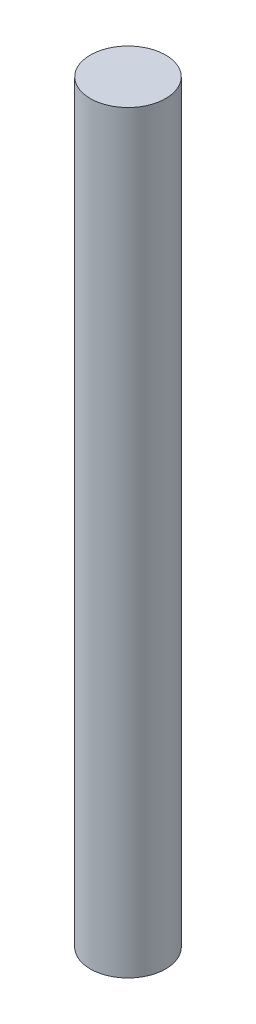
SolidWorks part; units mm, degrees
other "Title Block Table1"
other "DetailItem1"
material "PA Type 6 - Black"
ref_plane "Front Plane" through (0, 0, 0) normal (0, 0, 1) x (1, 0, 0)
ref_plane "Top Plane" through (0, 0, 0) normal (0, 1, 0) x (1, 0, 0)
ref_plane "Right Plane" through (0, 0, 0) normal (1, 0, 0) x (0, 0, -1)
ref_axis "X-Axis" through (-83.7009, 0, 0) along (1, 0, 0)
ref_axis "Y-Axis" through (0, 70.1691, 0) along (0, -1, 0)
ref_axis "Z-Axis" through (0, 0, -88.99) along (0, 0, 1)
sketch "Sketch1" plane through (0, 0, 0) normal (0, 1, 0) x (1, 0, 0)
  circle A0 centre (0, 0) radius 10
  dimension "D1" = 20
extrude "Boss-Extrude1" add sketch "Sketch1" along normal blind 200
